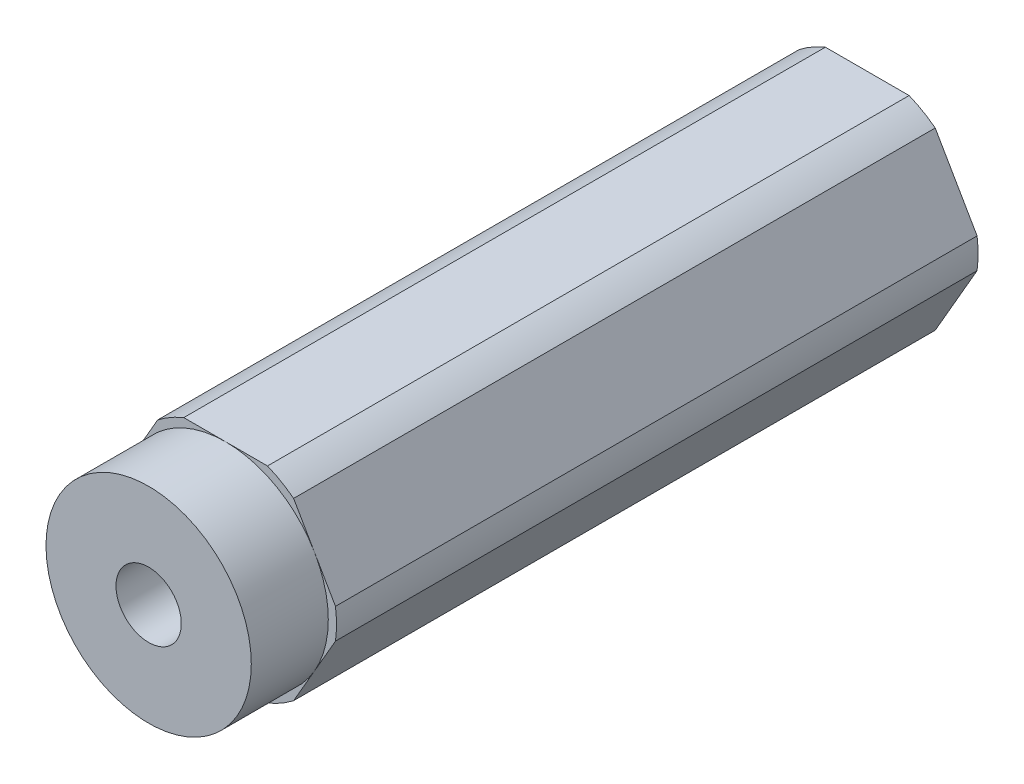
SolidWorks part; units mm, degrees
ref_plane "Front Plane" through (0, 0, 0) normal (0, 0, 1) x (1, 0, 0)
ref_plane "Top Plane" through (0, 0, 0) normal (0, 1, 0) x (1, 0, 0)
ref_plane "Right Plane" through (0, 0, 0) normal (1, 0, 0) x (0, 0, -1)
sketch "Sketch1" plane through (0, 0, 0) normal (0, 0, 1) x (1, 0, 0)
  line L1 (3.6662, 6.35) -> (-3.6662, 6.35)
  line L2 (-3.6662, 6.35) -> (-7.3323, 0)
  line L3 (-7.3323, 0) -> (-3.6662, -6.35)
  line L4 (-3.6662, -6.35) -> (3.6662, -6.35)
  line L5 (3.6662, -6.35) -> (7.3323, 0)
  line L6 (7.3323, 0) -> (3.6662, 6.35)
  circle A0 centre (0, 0) radius 6.35 construction
  circle A1 centre (0, 0) radius 6.858
  circle A2 centre (0, 0) radius 2.0193
  dimension "D1" = 12.7
  dimension "D2" = 13.716
  dimension "D3" = 4.0386
extrude "Boss-Extrude1" add sketch "Sketch1" along normal mid plane 39.6875 contours L6 A1 L1 L2 L3 L4 L5 A2 region at (3.3355, 5.7773, 0)
sketch "Sketch2" plane through (0, 0, 19.8438) normal (0, 0, 1) x (1, 0, 0)
  circle A0 centre (0, 0) radius 6.35
  circle A1 centre (0, 0) radius 2.0193
  dimension "D1" = 12.7
  dimension "D2" = 4.0386
extrude "Boss-Extrude2" add sketch "Sketch2" along normal mid plane 9.525
